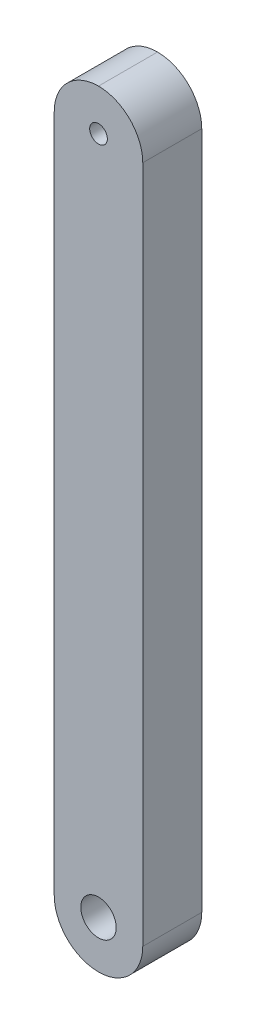
SolidWorks part; units mm, degrees
ref_plane "Front" through (0, 0, 0) normal (0, 0, 1) x (1, 0, 0)
ref_plane "Top" through (0, 0, 0) normal (0, 1, 0) x (1, 0, 0)
ref_plane "Right" through (0, 0, 0) normal (1, 0, 0) x (0, 0, -1)
sketch "Esquisse1" plane through (0, 0, 0) normal (0, 0, 1) x (1, 0, 0)
  line L1 (0, 0) -> (15, 0)
  line L2 (0, 0) -> (0, 130)
  line L3 (0, 130) -> (15, 130)
  line L4 (15, 0) -> (15, 130)
  dimension "D1" = 15
  dimension "D2" = 130
extrude "Boss.-Extru.1" add sketch "Esquisse1" along normal blind 10
sketch "Esquisse2" plane through (0, 0, 10) normal (0, 0, 1) x (1, 0, 0)
  line L0 (7.5, 123) -> (7.5, 130) construction
  line L1 (15, 130) -> (0, 130) construction
  line L2 (0, 0) -> (15, 0) construction
  line L3 (7.5, 8) -> (7.5, 0) construction
  circle A1 centre (7.5, 123) radius 1.5
  circle A2 centre (7.5, 8) radius 3
  point P11 (7.5, 0)
  dimension "D2" = 7
  dimension "D3" = 3
  dimension "D4" = 6
  dimension "D5" = 8
extrude "Enlèv. mat.-Extru.1" cut sketch "Esquisse2" against normal up to vertex (10 mm away) up to point (0, 130, 0)
fillet "Congé1" radius 7.5 4 edges at (15, 130, 5) (0, 130, 5) (15, 0, 5) (0, 0, 5)
